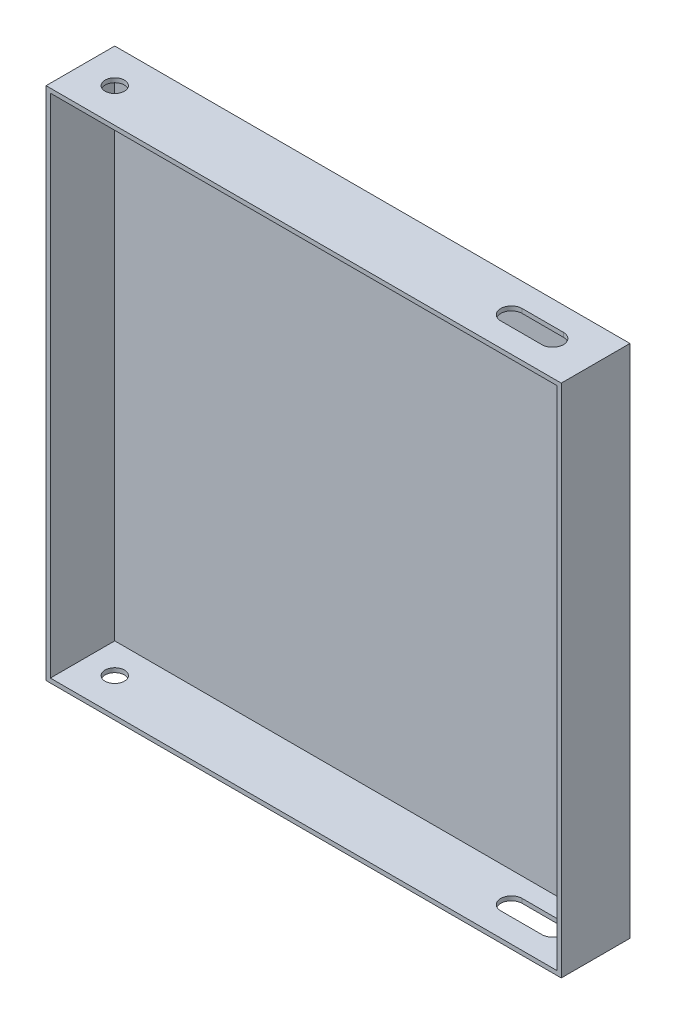
SolidWorks part; units mm, degrees
ref_plane "Front Plane" through (0, 0, 0) normal (0, 0, 1) x (1, 0, 0)
ref_plane "Top Plane" through (0, 0, 0) normal (0, 1, 0) x (1, 0, 0)
ref_plane "Right Plane" through (0, 0, 0) normal (1, 0, 0) x (0, 0, -1)
sketch "Sketch1" plane through (0, 0, 0) normal (0, 0, 1) x (1, 0, 0)
  line L1 (0, 0) -> (381, 0)
  line L2 (0, 0) -> (0, 381)
  line L3 (0, 381) -> (381, 381)
  line L4 (381, 0) -> (381, 381)
  dimension "D1" = 381
  dimension "D2" = 381
extrude "Boss-Extrude1" add sketch "Sketch1" along normal blind 50.8
shell "Shell1" thickness 3.175 removed face at (190.5, 190.5, 50.8)
sketch "Sketch2" plane through (0, 381, 0) normal (0, 1, 0) x (1, 0, 0)
  line L0 (349.25, -25.4) -> (318.77, -25.4) construction
  line L1 (349.25, -33.3375) -> (318.77, -33.3375)
  line L2 (349.25, -17.4625) -> (318.77, -17.4625)
  line L3 (0, -25.4) -> (25.4, -25.4) construction
  line L4 (0, -50.8) -> (0, 0) construction
  circle A0 centre (25.4, -25.4) radius 7.1437
  arc A1 (349.25, -33.3375) -> (349.25, -17.4625) centre (349.25, -25.4) ccw
  arc A2 (318.77, -17.4625) -> (318.77, -33.3375) centre (318.77, -25.4) ccw
  point P7 (334.01, -25.4)
  point P12 (0, 0)
  point P13 (0, 0)
  dimension "D1" = 14.2875
  dimension "D4" = 15.875
  dimension "D2" = 293.37
  dimension "D3" = 25.4
  dimension "D5" = 30.48
extrude "Cut-Extrude1" cut sketch "Sketch2" against normal blind 417.576
ref_plane "Plane1" through (349.25, 381, 17.4625) normal (-1, 0, 0) x (0, 0, 1)
